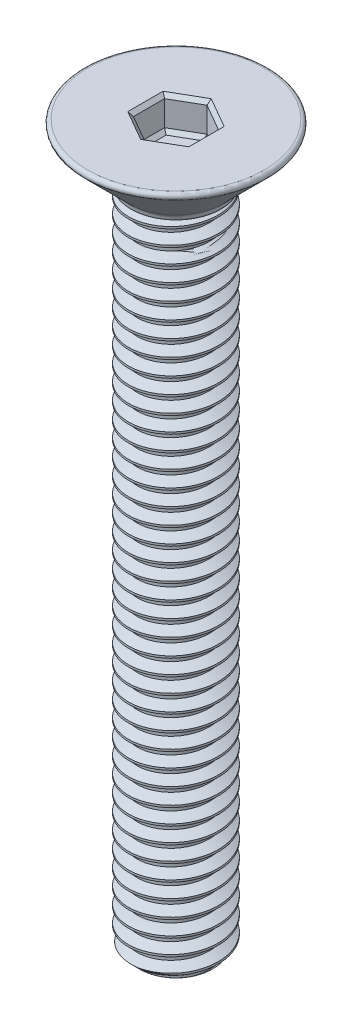
SolidWorks part; units mm, degrees
material "AISI Type A2 Tool Steel"
ref_plane "Front Plane" through (0, 0, 0) normal (0, 0, 1) x (1, 0, 0)
ref_plane "Top Plane" through (0, 0, 0) normal (0, 1, 0) x (1, 0, 0)
ref_plane "Right Plane" through (0, 0, 0) normal (1, 0, 0) x (0, 0, -1)
sketch "Sketch1" plane through (0, 0, 0) normal (0, 1, 0) x (1, 0, 0)
  circle A0 centre (0, 0) radius 1.25
  dimension "D1" = 2.5
extrude "Boss-Extrude1" add sketch "Sketch1" along normal blind 18.45
thread "Thread1" pitch 0.45 start angle 0, offset 1, length 0, pitch 0.45, diameter 2.5
ref_plane "Plane1" through (1.25, -1, 0) normal (0, 0, 1) x (1, 0, 0)
sketch "Thread Profile1" plane through (1.25, -1, 0) normal (0, 0, 1) x (1, 0, 0)
  line L0 (0, 0) -> (0, 0.45) construction
  line L11 (0, 0) -> (0, 0.3937)
  line L12 (0, 0.3937) -> (-0.2436, 0.2531)
  line L13 (-0.2436, 0.2531) -> (-0.2436, 0.1406)
  line L15 (-0.2436, 0.1406) -> (0, 0)
  line L17 (-0.2436, 0.1969) -> (0, 0.1969) construction
  point P2 (0, 0)
  dimension "Pitch" = 0.45
  dimension "Profile_Angle" = 60
  dimension "Profile_Land" = 0.1125
  dimension "Profile_Height" = 0.2436
sketch "Sketch5" plane through (0, 18.45, 0) normal (0, 1, 0) x (1, 0, 0)
  circle A0 centre (0, 0) radius 1.25
  dimension "D1" = 2.5
extrude "Boss-Extrude2" add sketch "Sketch5" along normal blind 0.1
sketch "Sketch6" plane through (0, 18.55, 0) normal (0, 1, 0) x (1, 0, 0)
  circle A0 centre (0, 0) radius 1.25
  dimension "D1" = 2.5
extrude "Boss-Extrude3" add sketch "Sketch6" along normal blind 1.45 draft 45
fillet "Fillet1" radius 0.2 1 edges at (0, 18.55, 1.25)
fillet "Fillet2" radius 0.1 1 edges at (0, 20, 2.7)
sketch "Sketch7" plane through (0, 0, 0) normal (0, 0, 1) x (1, 0, 0)
  line L0 (0, 0) -> (0, 0.3237) construction
  line L1 (0, 0) -> (1.26, 0) construction
  line L2 (1.26, 0) -> (1.26, 0.26)
  line L3 (1.26, 0.26) -> (1, 0)
  line L4 (1, 0) -> (1.26, 0)
  dimension "D1" = 45
  dimension "D2" = 0.26
  dimension "D3" = 1.26
revolve "Cut-Revolve1" cut sketch "Sketch7" angle 360 about L0
sketch "Sketch8" plane through (0, 20, 0) normal (0, 1, 0) x (1, 0, 0)
  line L1 (0, 0.866) -> (-0.75, 0.433)
  line L2 (-0.75, 0.433) -> (-0.75, -0.433)
  line L3 (-0.75, -0.433) -> (0, -0.866)
  line L4 (0, -0.866) -> (0.75, -0.433)
  line L5 (0.75, -0.433) -> (0.75, 0.433)
  line L6 (0.75, 0.433) -> (0, 0.866)
  circle A0 centre (0, 0) radius 0.75 construction
  dimension "D1" = 1.5
extrude "Cut-Extrude1" cut sketch "Sketch8" against normal blind 0.8
chamfer "Chamfer1" distance 0.1 angle 45 6 edges at (-0.75, 20, 0) (-0.375, 20, 0.6495) (0.375, 20, 0.6495) (0.75, 20, 0) (0.375, 20, -0.6495) (-0.375, 20, -0.6495)
sketch "Sketch9" plane through (0, 19.2, 0) normal (0, 1, 0) x (1, 0, 0)
  line L1 (0, 0.866) -> (-0.75, 0.433)
  line L2 (-0.75, 0.433) -> (-0.75, -0.433)
  line L3 (-0.75, -0.433) -> (0, -0.866)
  line L4 (0, -0.866) -> (0.75, -0.433)
  line L5 (0.75, -0.433) -> (0.75, 0.433)
  line L6 (0.75, 0.433) -> (0, 0.866)
  circle A0 centre (0, 0) radius 0.75 construction
extrude "Cut-Extrude2" cut sketch "Sketch9" against normal blind 0.1 draft 45
